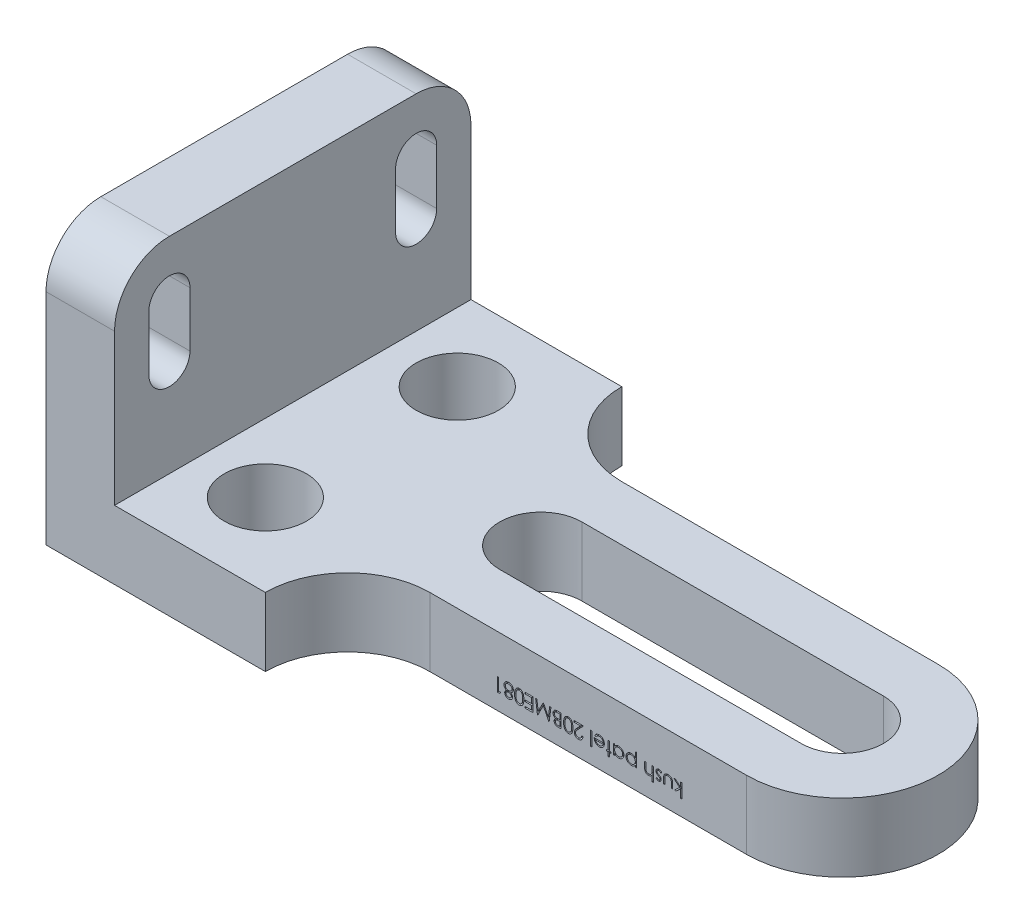
SolidWorks part; units mm, degrees
ref_plane "Front Plane" through (0, 0, 0) normal (0, 0, 1) x (1, 0, 0)
ref_plane "Top Plane" through (0, 0, 0) normal (0, 1, 0) x (1, 0, 0)
ref_plane "Right Plane" through (0, 0, 0) normal (1, 0, 0) x (0, 0, -1)
sketch "Sketch1" plane through (0, 0, 0) normal (0, 1, 0) x (1, 0, 0)
  line L0 (0, 0) -> (0, 52)
  line L1 (0, 52) -> (32, 52)
  line L2 (0, 0) -> (32, 0)
  line L4 (44, 40) -> (90.1768, 40)
  line L6 (90.1768, 12) -> (44, 12)
  line L9 (90.1768, 32) -> (46.1768, 32)
  line L10 (90.1768, 20) -> (46.1768, 20)
  line L13 (0, 52) -> (10, 52)
  line L14 (0, 52) -> (0, 0)
  line L15 (0, 0) -> (10, 0)
  line L16 (10, 52) -> (10, 0)
  arc A1 (32, 0) -> (44, 12) centre (44, 0) cw
  arc A2 (32, 52) -> (44, 40) centre (44, 52) ccw
  arc A5 (90.1768, 12) -> (90.1768, 40) centre (90.1768, 26) ccw
  arc A6 (90.1768, 20) -> (90.1768, 32) centre (90.1768, 26) ccw
  arc A7 (46.1768, 32) -> (46.1768, 20) centre (46.1768, 26) ccw
  circle A8 centre (20, 40) radius 6
  circle A9 centre (20, 12) radius 6
  dimension "D4" = 44
  dimension "D5" = 10
  dimension "D7" = 12
  dimension "D1" = 32
  dimension "D2" = 52
  dimension "D3" = 32
  dimension "D6" = 28
  dimension "D8" = 20
extrude "Boss-Extrude1" add sketch "Sketch1" along normal blind 10 contours L6 A5 L4 A2 L1 L16 L2 A1 A9 A8 A7 L9 A6 L10 region at (11.0758, 0, -26)
extrude "Boss-Extrude2" add sketch "Sketch1<3>" along normal blind 40 contours L16 L1 L0 L2 region at (5, 0, -26)
sketch "Sketch1<3>" plane through (0, 0, 0) normal (0, 1, 0) x (1, 0, 0) same geometry as "Sketch1"
sketch "Sketch2" plane through (10, 0, 0) normal (1, 0, 0) x (0, 0, -1)
  line L9 (10.9618, 49.2538) -> (5, 48.5778)
  line L10 (10.9618, 57.2285) -> (10.9618, 49.2538)
  line L11 (5, 56.5778) -> (10.9618, 57.2285)
  line L12 (5, 48.5778) -> (5, 56.5778)
  line L19 (11, 32) -> (11, 24)
  line L21 (5, 24) -> (5, 32)
  line L24 (41, 31.9962) -> (41, 24)
  line L26 (47, 24) -> (47, 31.9962)
  arc A2 (5, 24) -> (11, 24) centre (8, 24) ccw
  arc A3 (11, 32) -> (5, 32) centre (8, 32) ccw
  arc A4 (47, 31.9962) -> (41, 31.9962) centre (44, 31.9962) ccw
  arc A5 (41, 24) -> (47, 24) centre (44, 24) ccw
extrude "Cut-Extrude1" cut sketch "Sketch2" against normal blind 10
fillet "Fillet1" radius 8 1 edges at (5, 40, 0)
fillet "Fillet2" radius 8 1 edges at (5, 40, -52)
sketch "Sketch3" plane through (0, 0, -12) normal (0, 0, 1) x (1, 0, 0)
  text T0 "\r\nkush patel 20BME081" font "Century Gothic" height 2
extrude "Cut-Extrude2" cut sketch "Sketch3" against normal blind 3
